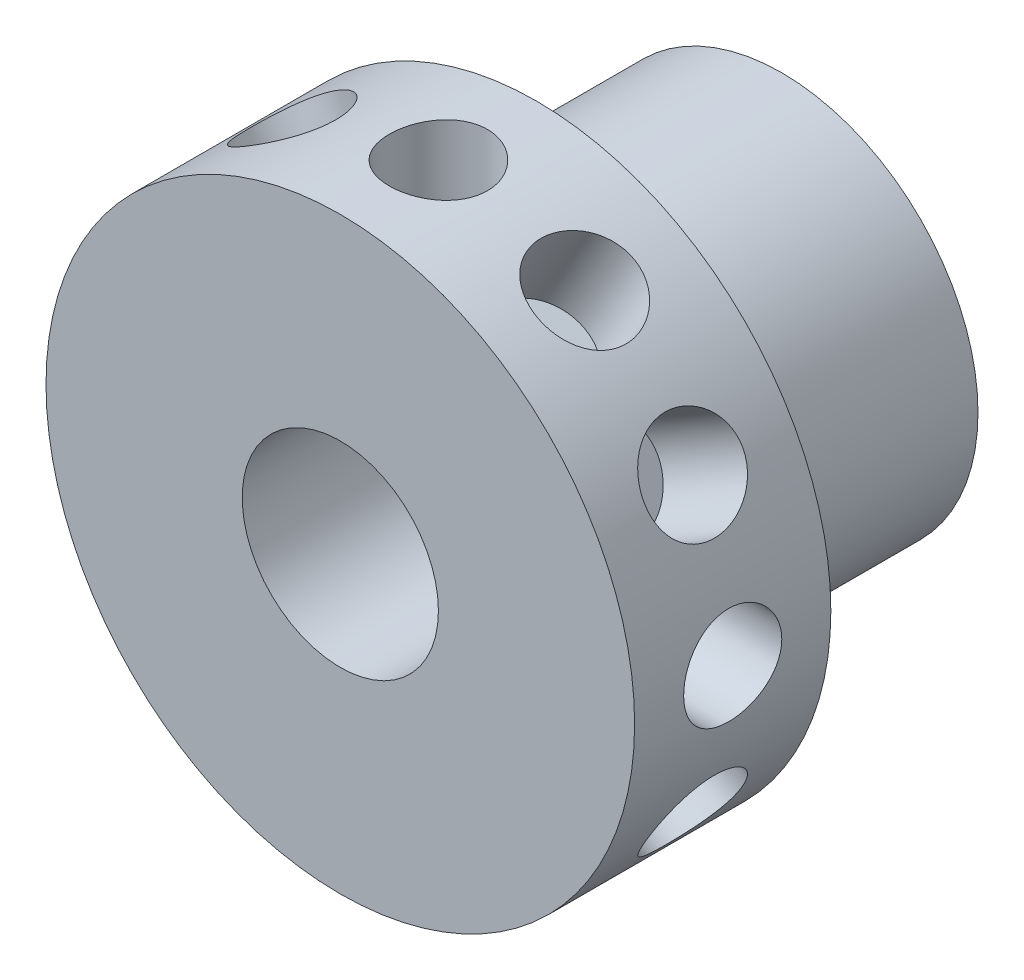
SolidWorks part; units mm, degrees
ref_plane "Front Plane" through (0, 0, 0) normal (0, 0, 1) x (1, 0, 0)
ref_plane "Top Plane" through (0, 0, 0) normal (0, 1, 0) x (1, 0, 0)
ref_plane "Right Plane" through (0, 0, 0) normal (1, 0, 0) x (0, 0, -1)
ref_axis "X" through (-88.99, 0, 0) along (1, 0, 0)
ref_axis "Y" through (0, 55, 0) along (0, -1, 0)
ref_axis "Z" through (0, 0, -88.99) along (0, 0, 1)
sketch "Sketch1" plane through (0, 0, 0) normal (0, 0, 1) x (1, 0, 0)
  circle A0 centre (0, 0) radius 2
  circle A1 centre (0, 0) radius 6
  circle A2 centre (0, 0) radius 4
  dimension "D1" = 4
  dimension "D3" = 8
  dimension "D2" = 4
extrude "Boss-Extrude1" add sketch "Sketch1" along normal mid plane 4 contours A1 A2 | A2 A0 region at (-5.8303, 0, 0) region at (-3.8869, 0, 0)
ref_plane "Plane1" through (0, -6, 0) normal (0, -1, 0) x (-1, 0, 0)
sketch "Sketch3" plane through (0, -6, 0) normal (0, -1, 0) x (-1, 0, 0)
  circle A0 centre (0, 0) radius 1
  dimension "D1" = 2
extrude "Cut-Extrude1" cut sketch "Sketch3" against normal blind 2
pattern_circular "CirPattern1" count 12 over 360 about axis through (0, 0, -88.99) along (0, 0, 1) of "Cut-Extrude1"
extrude "Boss-Extrude2" add sketch "Sketch1<3>" against normal blind 5 from surface contours A2 A0 region at (-3.8869, 0, 0) starting at face at (6, 0, -2)
sketch "Sketch1<3>" plane through (0, 0, 0) normal (0, 0, 1) x (1, 0, 0) same geometry as "Sketch1"
equation "\"Axle Diameter\"= 0.4cm"
equation "\"D1@Sketch1\"=\"Axle Diameter\""
